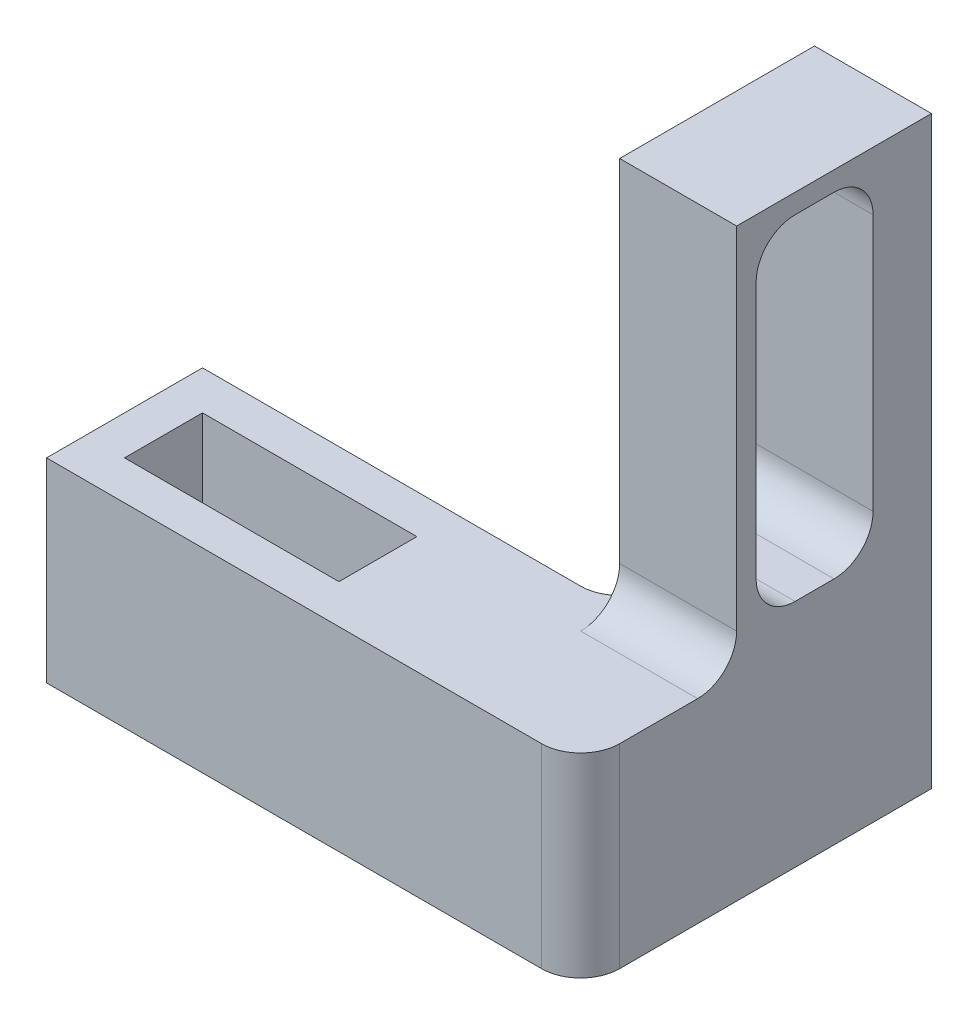
SolidWorks part; units mm, degrees
ref_plane "Front Plane" through (0, 0, 0) normal (0, 0, 1) x (1, 0, 0)
ref_plane "Top Plane" through (0, 0, 0) normal (0, 1, 0) x (1, 0, 0)
ref_plane "Right Plane" through (0, 0, 0) normal (1, 0, 0) x (0, 0, -1)
sketch "Sketch1" plane through (0, 0, 0) normal (0, 1, 0) x (1, 0, 0)
  line L1 (-2.5135, 3.907) -> (2.9865, 3.907)
  line L2 (-2.5135, 3.907) -> (-2.5135, 1.907)
  line L3 (-2.5135, 1.907) -> (2.9865, 1.907)
  line L4 (2.9865, 3.907) -> (2.9865, 1.907)
  line L5 (-3.5135, 4.907) -> (3.9865, 4.907)
  line L6 (-3.5135, 4.907) -> (-3.5135, 0.907)
  line L7 (-3.5135, 0.907) -> (3.9865, 0.907)
  line L8 (3.9865, 4.907) -> (3.9865, 0.907)
  dimension "D1" = 2
  dimension "D2" = 5.5
  dimension "D3" = 1
  dimension "D4" = 1
  dimension "D5" = 1
  dimension "D6" = 1
extrude "Boss-Extrude1" add sketch "Sketch1" along normal blind 5
sketch "Sketch2" plane through (0, 0, -4.907) normal (0, 0, -1) x (-1, 0, 0)
  line L1 (-3.9865, 5) -> (-10.1865, 5)
  line L2 (-3.9865, 5) -> (-3.9865, 0)
  line L3 (-3.9865, 0) -> (-10.1865, 0)
  line L4 (-10.1865, 5) -> (-10.1865, 0)
  circle A0 centre (-0.2365, 2.5) radius 6.5 construction
  dimension "D1" = 13
  dimension "D2" = 6.2
extrude "Boss-Extrude2" add sketch "Sketch2" against normal blind 4
sketch "Sketch3" plane through (0, 0, -4.907) normal (0, 0, -1) x (-1, 0, 0)
  line L0 (-10.1865, 0) -> (3.5135, 0) construction
  line L1 (-10.1865, 5) -> (-7.1865, 5)
  line L2 (-10.1865, 5) -> (-10.1865, 0)
  line L3 (-10.1865, 0) -> (-7.1865, 0)
  line L4 (-7.1865, 5) -> (-7.1865, 0)
  dimension "D1" = 3
extrude "Boss-Extrude3" add sketch "Sketch3" along normal blind 5
sketch "Sketch4" plane through (0, 5, 0) normal (0, 1, 0) x (1, 0, 0)
  line L0 (10.1865, 0.907) -> (10.1865, 9.907) construction
  line L1 (7.1865, 9.907) -> (10.1865, 9.907)
  line L2 (7.1865, 9.907) -> (7.1865, 4.9094)
  line L3 (7.1865, 4.9094) -> (10.1865, 4.9094)
  line L4 (10.1865, 9.907) -> (10.1865, 4.9094)
extrude "Boss-Extrude4" add sketch "Sketch4" along normal blind 10
sketch "Sketch5" plane through (10.1865, 0, 0) normal (1, 0, 0) x (0, 0, -1)
  line L0 (4.9094, 15) -> (4.9094, 5) construction
  line L1 (5.4094, 14.5) -> (8.4094, 14.5)
  line L2 (5.4094, 14.5) -> (5.4094, 5.9101)
  line L3 (5.4094, 5.9101) -> (8.4094, 5.9101)
  line L4 (8.4094, 14.5) -> (8.4094, 5.9101)
  line L5 (4.9094, 15) -> (9.907, 15) construction
  dimension "D1" = 0.5
  dimension "D2" = 3
  dimension "D3" = 0.5
extrude "Cut-Extrude1" cut sketch "Sketch5" against normal blind 10
fillet "Fillet1" radius 1 1 edges
fillet "Fillet2" radius 1 1 edges at (10.1865, 2.5, -0.907)
fillet "Fillet3" radius 1 1 edges
sketch "Sketch6" plane through (0, 15, 0) normal (0, 1, 0) x (1, 0, 0)
  line L1 (7.1865, 5.907) -> (-3.5135, 5.907)
  line L2 (7.1865, 5.907) -> (7.1865, 3.9094)
  line L3 (7.1865, 3.9094) -> (-3.5135, 3.9094)
  line L4 (-3.5135, 5.907) -> (-3.5135, 3.9094)
extrude "Cut-Extrude2" cut sketch "Sketch6" against normal blind 10
fillet "Fillet4" radius 1 1 edges at (8.6865, 5.9101, -8.4094)
fillet "Fillet5" radius 1 1 edges at (8.6865, 5.9101, -5.4094)
fillet "Fillet6" radius 1 1 edges at (8.6865, 14.5, -5.4094)
fillet "Fillet7" radius 1 1 edges at (8.6865, 14.5, -8.4094)
